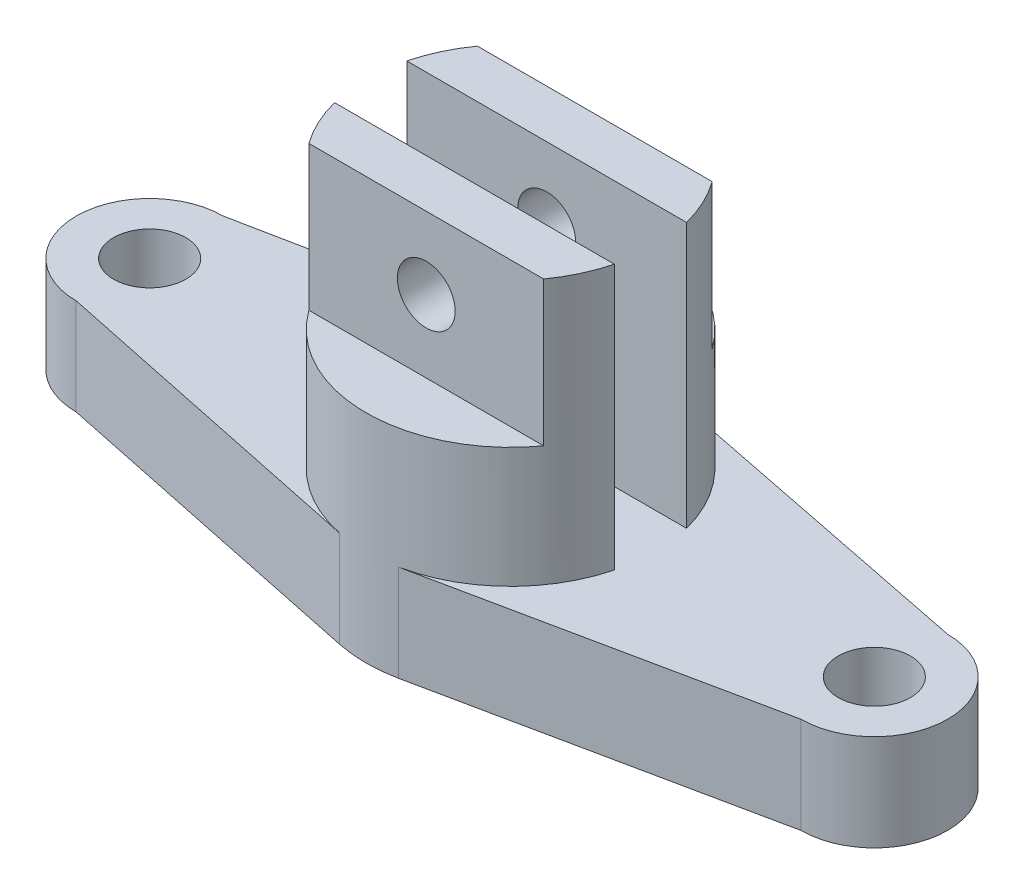
SolidWorks part; units mm, degrees
ref_plane "Alzado" through (0, 0, 0) normal (0, 0, 1) x (1, 0, 0)
ref_plane "Planta" through (0, 0, 0) normal (0, 1, 0) x (1, 0, 0)
ref_plane "Vista lateral" through (0, 0, 0) normal (1, 0, 0) x (0, 0, -1)
sketch "Croquis2" plane through (0, 0, 0) normal (0, 1, 0) x (1, 0, 0)
  line L0 (-75.2235, -14.9523) -> (-6.1269, -29.3677)
  line L1 (-75.2235, 15.5494) -> (-5.8835, 29.4174)
  line L2 (6.1269, -29.3677) -> (75.2235, -14.9523)
  line L3 (75.2235, 15.5494) -> (5.8835, 29.4174)
  line L6 (-29.0474, 7.5) -> (29.0474, 7.5)
  line L7 (-29.0474, -7.5) -> (29.0474, -7.5)
  line L8 (-24.367, 17.5) -> (24.367, 17.5)
  line L9 (-24.367, -17.5) -> (24.367, -17.5)
  arc A0 (-29.0474, -7.5) -> (29.0474, -7.5) centre (0, 0) ccw
  circle A1 centre (-75.2235, 0.2985) radius 7.5
  arc A2 (-75.2235, 15.5494) -> (-75.2235, -14.9523) centre (-75.2235, 0.2985) ccw
  circle A3 centre (75.2235, 0.2985) radius 7.5
  arc A4 (75.2235, -14.9523) -> (75.2235, 15.5494) centre (75.2235, 0.2985) ccw
  arc A5 (29.0474, 7.5) -> (-29.0474, 7.5) centre (0, 0) ccw
  dimension "D1" = 60
sketch "Croquis4" plane through (0, 0, 0) normal (0, 0, 1) x (1, 0, 0)
  line L0 (-90, 0) -> (-90, 20)
  line L1 (-75.2235, 0) -> (-90.4744, 0) construction
  line L2 (90, 0) -> (90, 20)
  line L3 (90.4744, 0) -> (75.2235, 0) construction
  line L4 (-90, 20) -> (90, 20)
  line L5 (-30, 75) -> (-25, 75)
  line L6 (30, 75) -> (-30, 75)
  line L7 (-30, 75) -> (-30, 20)
  line L8 (30, 75) -> (30, 20)
  line L9 (25, 75) -> (25, 45)
  line L10 (25, 45) -> (-25, 45)
  line L11 (-25, 75) -> (-25, 43.799)
  circle A0 centre (0, 60) radius 6
sketch "Croquis5" plane through (0, 0, 0) normal (1, 0, 0) x (0, 0, -1)
  line L0 (30, 0) -> (30, 20)
  line L1 (30, 0) -> (7.5, 0) construction
  line L2 (30, 20) -> (-30, 20)
  line L3 (-30, 0) -> (-30, 20)
  line L4 (-7.5, 0) -> (-30, 0) construction
  line L5 (30, 45) -> (30, 20)
  line L8 (30, 45) -> (17.5, 45)
  line L9 (7.5, 75) -> (17.5, 75)
  line L10 (17.5, 45) -> (17.5, 75)
  line L11 (7.5, 75) -> (7.5, 0) construction
  line L13 (15.5494, 0) -> (-14.9523, 0) construction
  line L14 (-7.5, 75) -> (-7.5, 0) construction
  line L15 (7.5, 54) -> (17.5, 54) construction
  line L17 (7.5, 66) -> (17.5, 66) construction
  line L18 (-7.5, 66) -> (-17.5, 66) construction
  line L19 (-7.5, 54) -> (-17.5, 54) construction
  line L20 (-17.5, 45) -> (-17.5, 75)
  line L21 (-7.5, 75) -> (-17.5, 75)
  line L22 (-30, 45) -> (-17.5, 45)
  line L23 (-30, 45) -> (-30, 20)
  line L24 (17.5, 0) -> (17.5, 20)
  line L25 (-17.5, 0) -> (-17.5, 20)
extrude "Saliente-Extruir1" add sketch "Croquis2" along normal blind 20 contours A5 L6 L1 A2 L0 A0 L7 L2 A4 L3 A1 A3 | A0 L9 | L9 A0 L7 | L6 A5 L8 | L8 A5 region at (0, 0, -0.1757) region at (0, 0, 22.6016) region at (0, 0, 12.3572) region at (0, 0, -22.6016) region at (0, 0, -12.3572)
extrude "Saliente-Extruir2" add sketch "Croquis2<3>" along normal blind 25 from surface contours A0 L9 | L9 A0 L7 | L6 A5 L8 | L8 A5 | L6 A5 region at (0, 0, 22.6016) region at (0, 0, 12.3572) region at (0, 0, -22.6016) region at (0, 0, -12.3572) starting at face at (0, 20, -0.1555)
sketch "Croquis2<3>" plane through (0, 0, 0) normal (0, 1, 0) x (1, 0, 0) same geometry as "Croquis2"
extrude "Saliente-Extruir3" add sketch "Croquis2<4>" along normal blind 30 from surface contours L9 A0 L7 | L6 A5 L8 region at (0, 0, 12.3572) region at (0, 0, -12.3572) starting at face at (0, 45, 18.75)
sketch "Croquis2<4>" plane through (0, 0, 0) normal (0, 1, 0) x (1, 0, 0) same geometry as "Croquis2"
extrude "Cortar-Extruir1" cut sketch "Croquis4" against normal through all both and the other way through all contours A0
